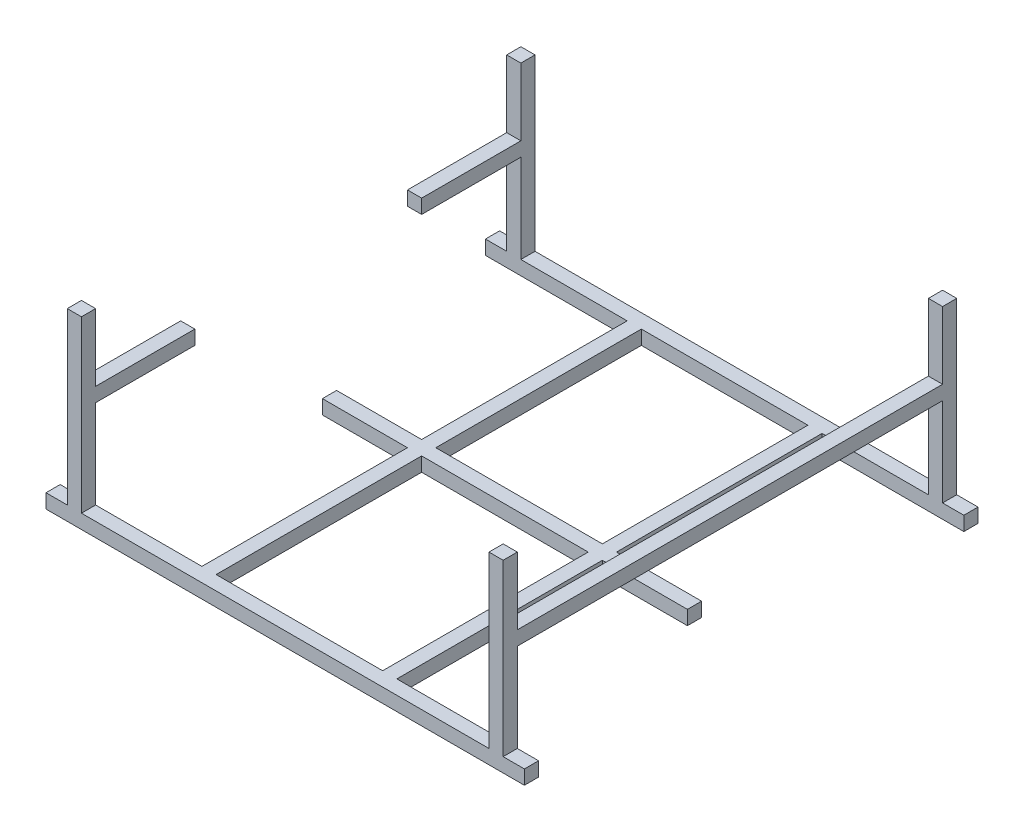
SolidWorks part; units mm, degrees
material "6061 合金"
ref_plane "前视基准面" through (0, 0, 0) normal (0, 0, 1) x (1, 0, 0)
ref_plane "上视基准面" through (0, 0, 0) normal (0, 1, 0) x (1, 0, 0)
ref_plane "右视基准面" through (0, 0, 0) normal (1, 0, 0) x (0, 0, -1)
sketch "草图1" plane through (0, 0, 0) normal (0, 1, 0) x (1, 0, 0)
  line L0 (-221.5101, -7.503) -> (-21.5101, -7.503)
  line L1 (-221.5101, 612.497) -> (453.4899, 612.497)
  line L2 (-221.5101, 612.497) -> (-221.5101, 592.497)
  line L3 (-221.5101, 592.497) -> (-21.5101, 592.497)
  line L4 (453.4899, 612.497) -> (453.4899, 592.497)
  line L5 (-221.5101, -7.503) -> (-221.5101, -27.503)
  line L6 (-221.5101, -27.503) -> (453.4899, -27.503)
  line L7 (453.4899, -7.503) -> (453.4899, -27.503)
  line L8 (253.4899, 592.497) -> (453.4899, 592.497)
  line L10 (-21.5101, 592.497) -> (-21.5101, -7.503)
  line L12 (-1.5101, 592.497) -> (-1.5101, -7.503)
  line L14 (253.4899, 592.497) -> (253.4899, -7.503)
  line L16 (233.4899, 592.497) -> (233.4899, -7.503)
  line L17 (253.4899, -7.503) -> (453.4899, -7.503)
  line L18 (-1.5101, -7.503) -> (233.4899, -7.503)
  line L19 (-1.5101, 592.497) -> (233.4899, 592.497)
  dimension "D1" = 20
  dimension "D2" = 675
  dimension "D3" = 20
  dimension "D4" = 675
  dimension "D5" = 640
  dimension "D6" = 20
  dimension "D7" = 200
  dimension "D8" = 220
  dimension "D9" = 20
extrude "凸台-拉伸1" add sketch "草图1" along normal blind 20
ref_plane "基准面1" through (-191.5101, 0, 0) normal (-1, 0, 0) x (0, 0, 1)
sketch "草图2" plane through (-191.5101, 0, 0) normal (-1, 0, 0) x (0, 0, 1)
  line L0 (27.503, 20) -> (27.503, 0) construction
  line L1 (27.503, 20) -> (7.503, 20)
  line L2 (27.503, 20) -> (27.503, 260)
  line L3 (27.503, 260) -> (7.503, 260)
  line L4 (7.503, 20) -> (7.503, 165)
  line L5 (27.503, 20) -> (7.503, 20) construction
  line L6 (-592.497, 260) -> (-592.497, 165)
  line L11 (-592.497, 20) -> (-612.497, 20)
  line L12 (-592.497, 20) -> (-592.497, 165)
  line L13 (-592.497, 260) -> (-612.497, 260)
  line L14 (-612.497, 20) -> (-612.497, 260)
  line L15 (7.503, 260) -> (7.503, 165)
  dimension "D1" = 20
  dimension "D2" = 240
  dimension "D3" = 240
extrude "凸台-拉伸4" add sketch "草图2" against normal blind 20
ref_plane "基准面4" through (115.9899, 0, 0) normal (1, 0, 0) x (0, 0, -1)
mirror "镜向3" about plane through (115.9899, 0, 0) normal (1, 0, 0) of "凸台-拉伸4"
ref_plane "基准面5" through (0, 0, -292.497) normal (0, 0, 1) x (1, 0, 0)
sketch "草图6" plane through (-191.5101, 0, 0) normal (-1, 0, 0) x (0, 0, 1)
  line L0 (27.503, 20) -> (27.503, 260) construction
  line L1 (-612.497, 165) -> (27.503, 165)
  line L2 (-612.497, 165) -> (-612.497, 145)
  line L3 (-612.497, 145) -> (27.503, 145)
  line L4 (27.503, 165) -> (27.503, 145)
  line L5 (-612.497, 20) -> (-592.497, 20) construction
  dimension "D1" = 20
  dimension "D2" = 145
extrude "凸台-拉伸6" add sketch "草图6" against normal blind 20
mirror "镜向6" about plane through (115.9899, 0, 0) normal (1, 0, 0) of "凸台-拉伸6"
sketch "Sketch1" plane through (-191.5101, 0, 0) normal (-1, 0, 0) x (0, 0, 1)
  line L0 (7.503, 165) -> (-592.497, 165) construction
  line L1 (-452.497, 165) -> (-132.497, 165)
  line L2 (-452.497, 165) -> (-452.497, 145)
  line L3 (-452.497, 145) -> (-132.497, 145)
  line L4 (-132.497, 165) -> (-132.497, 145)
  line L5 (-592.497, 145) -> (7.503, 145) construction
  line L6 (-612.497, 260) -> (-612.497, 20) construction
  line L7 (27.503, 20) -> (27.503, 260) construction
  dimension "D1" = 160
  dimension "D2" = 160
extrude "Cut-Extrude1" cut sketch "Sketch1" against normal blind 20
sketch "Sketch2" plane through (0, 0, 0) normal (0, -1, 0) x (-1, 0, 0)
  line L0 (-253.4899, 292.497) -> (-301.1658, 292.497) construction
  line L1 (-373.4899, 282.497) -> (141.5101, 282.497)
  line L2 (-373.4899, 282.497) -> (-373.4899, 302.497)
  line L3 (-373.4899, 302.497) -> (141.5101, 302.497)
  line L4 (141.5101, 282.497) -> (141.5101, 302.497)
  line L5 (-253.4899, -7.503) -> (-253.4899, 592.497) construction
  line L8 (21.5101, 592.497) -> (21.5101, -7.503) construction
  dimension "D1" = 10
  dimension "D2" = 10
  dimension "D3" = 120
  dimension "D4" = 120
extrude "Extrude1" add sketch "Sketch2" against normal blind 20
